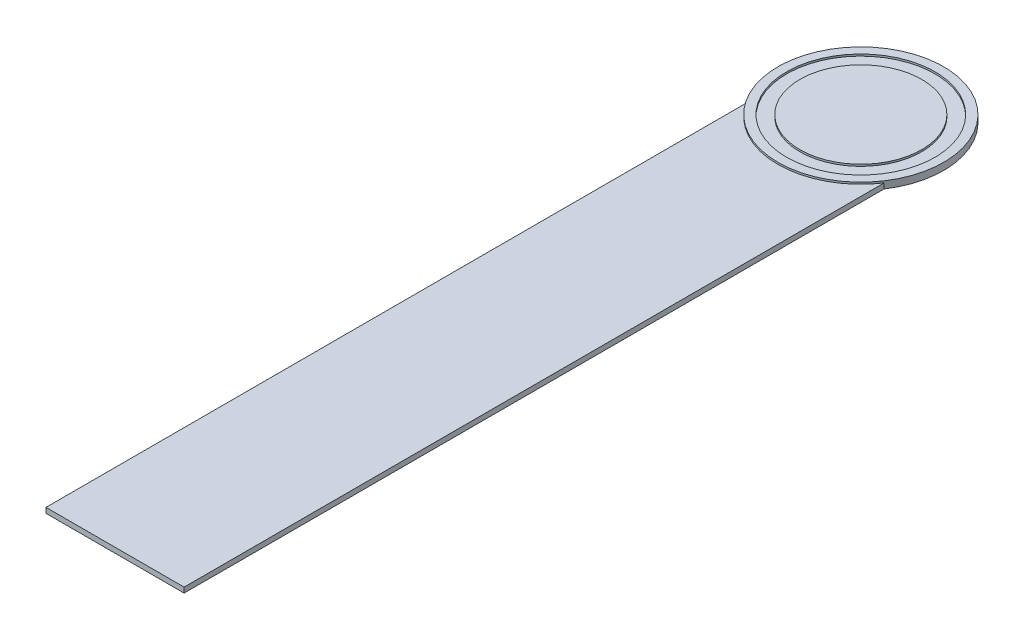
SolidWorks part; units mm, degrees
ref_plane "Front Plane" through (0, 0, 0) normal (0, 0, 1) x (1, 0, 0)
ref_plane "Top Plane" through (0, 0, 0) normal (0, 1, 0) x (1, 0, 0)
ref_plane "Right Plane" through (0, 0, 0) normal (1, 0, 0) x (0, 0, -1)
sketch "Sketch1" plane through (0, 0, 0) normal (0, 1, 0) x (1, 0, 0)
  line L0 (-3.175, -2.1061) -> (-3.175, -34.29)
  line L1 (3.175, -2.1061) -> (3.175, -34.29)
  line L2 (3.175, -34.29) -> (-3.175, -34.29)
  line L3 (0, 0) -> (0, -34.29) construction
  line L4 (-3.175, -27.29) -> (3.175, -27.29)
  circle A0 centre (0, 0) radius 3.81
  circle A1 centre (0, 0) radius 2.8
  circle A2 centre (0, 0) radius 3.41
  dimension "D1" = 7.62
  dimension "D5" = 5.6
  dimension "D6" = 0.4
  dimension "D2" = 6.35
  dimension "D3" = 38.1
  dimension "D4" = 7
extrude "Boss-Extrude1" add sketch "Sketch1" along normal blind 0.325 contours A1 | A2 A0 region at (-1.0687, 0, -3.5446) region at (0, 0, 0)
extrude "Boss-Extrude2" add sketch "Sketch1<3>" along normal blind 0.24 contours A1 A2 | L3 A0 L0 L4 | A0 L3 L4 L1 | L4 L3 L2 L1 | L3 L4 L0 L2 region at (-1.6051, 0, 15.2926) region at (-2.343, 0, -2.343) region at (-1.5875, 0, 30.79) region at (1.6051, 0, 15.2926) region at (1.5875, 0, 30.79)
sketch "Sketch1<3>" plane through (0, 0, 0) normal (0, 1, 0) x (1, 0, 0) same geometry as "Sketch1"
